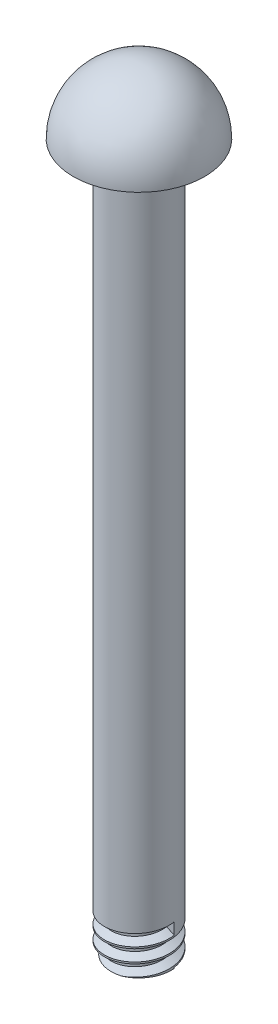
SolidWorks part; units mm, degrees
ref_plane "Front Plane" through (0, 0, 0) normal (0, 0, 1) x (1, 0, 0)
ref_plane "Top Plane" through (0, 0, 0) normal (0, 1, 0) x (1, 0, 0)
ref_plane "Right Plane" through (0, 0, 0) normal (1, 0, 0) x (0, 0, -1)
sketch "Sketch2" plane through (0, 0, 0) normal (0, 1, 0) x (1, 0, 0)
  circle A0 centre (0, 0) radius 12.4
extrude "Boss-Extrude1" add sketch "Sketch2" along normal blind 183
sketch "Sketch3" plane through (0, 183, 0) normal (0, 1, 0) x (1, 0, 0)
  circle A0 centre (0, 0) radius 25
extrude "Boss-Extrude2" add sketch "Sketch3" along normal blind 25 contours A0
fillet "Fillet1" radius 25 1 edges at (0, 208, 25)
sketch "Sketch4" plane through (0, 0, 0) normal (0, -1, 0) x (1, 0, 0)
  circle A0 centre (0, 0) radius 12.4
extrude "Boss-Extrude5" add sketch "Sketch4" along normal blind 85
thread "Thread3" pitch 5 method cut profile "Thread Profile5" start angle 5, offset 4, length 15, pitch 5, diameter 24.8
ref_plane "Plane5" through (12.3528, -89, -1.0807) normal (0.0872, 0, 0.9962) x (0.9962, 0, -0.0872)
sketch "Thread Profile5" plane through (12.3528, -89, -1.0807) normal (0.0872, 0, 0.9962) x (0.9962, 0, -0.0872)
  line L0 (0, 0) -> (0, 5) construction
  line L11 (0, 0) -> (0, 4.375)
  line L12 (0, 4.375) -> (-2.7063, 2.8125)
  line L13 (-2.7063, 2.8125) -> (-2.7063, 1.5625)
  line L15 (-2.7063, 1.5625) -> (0, 0)
  line L17 (-2.7063, 2.1875) -> (0, 2.1875) construction
  point P2 (0, 0)
  dimension "Pitch" = 5
  dimension "Profile_Angle" = 60
  dimension "Profile_Land" = 1.25
  dimension "Profile_Height" = 2.7063
sketch "Sketch35" plane through (0, -85, 0) normal (0, -1, 0) x (-1, 0, 0)
  circle A0 centre (0, 0) radius 19.9978
extrude "Cut-Extrude3" cut sketch "Sketch35" along normal blind 70 contours A0 rebuild error yes
